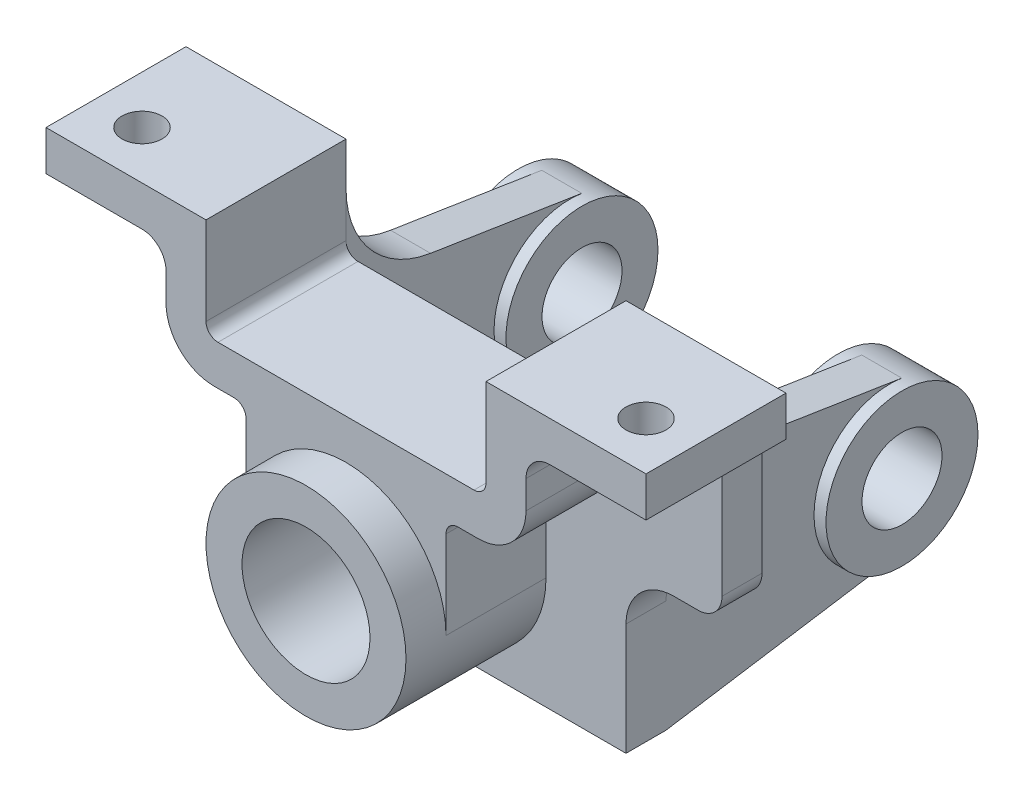
SolidWorks part; units mm, degrees
ref_plane "Ön Düzlem" through (0, 0, 0) normal (0, 0, 1) x (1, 0, 0)
ref_plane "Üst Düzlem" through (0, 0, 0) normal (0, 1, 0) x (1, 0, 0)
ref_plane "Sağ Düzlem" through (0, 0, 0) normal (1, 0, 0) x (0, 0, -1)
sketch "Çizim1" plane through (0, 0, 0) normal (0, 0, 1) x (1, 0, 0)
  circle A0 centre (0, 0) radius 16
  circle A1 centre (0, 0) radius 25
  dimension "D1" = 32
  dimension "D2" = 50
extrude "Yükseklik-Ekstrüzyon1" add sketch "Çizim1" against normal blind 45
ref_plane "Düzlem1" through (0, 0, -10) normal (0, 0, 1) x (1, 0, 0)
sketch "Çizim4" plane through (0, 0, -10) normal (0, 0, 1) x (1, 0, 0)
  line L0 (25, 0) -> (25, 22)
  line L1 (28, 25) -> (33, 25)
  line L2 (45, 37) -> (45, 44)
  line L3 (51, 50) -> (75, 50)
  line L4 (75, 50) -> (75, 60)
  line L5 (75, 60) -> (35, 60)
  line L6 (35, 60) -> (35, 38)
  line L7 (32, 35) -> (-32, 35)
  line L8 (0, 0) -> (0, 55.578) construction
  line L9 (-35, 60) -> (-35, 38)
  line L10 (-75, 60) -> (-35, 60)
  line L11 (-75, 50) -> (-75, 60)
  line L12 (-51, 50) -> (-75, 50)
  line L13 (-45, 37) -> (-45, 44)
  line L14 (-28, 25) -> (-33, 25)
  line L15 (-25, 0) -> (-25, 22)
  circle A0 centre (0, 0) radius 25 construction
  arc A1 (25, 22) -> (28, 25) centre (28, 22) cw
  arc A2 (33, 25) -> (45, 37) centre (33, 37) ccw
  arc A3 (45, 44) -> (51, 50) centre (51, 44) cw
  arc A4 (35, 38) -> (32, 35) centre (32, 38) cw
  arc A5 (-35, 38) -> (-32, 35) centre (-32, 38) ccw
  arc A6 (-45, 44) -> (-51, 50) centre (-51, 44) ccw
  arc A7 (-33, 25) -> (-45, 37) centre (-33, 37) cw
  arc A8 (-25, 22) -> (-28, 25) centre (-28, 22) ccw
  arc A9 (25, 0) -> (-25, 0) centre (0, 0) ccw
  point P23 (0, 35)
  dimension "D3" = 6
  dimension "D4" = 12
  dimension "D5" = 3
  dimension "D6" = 3
  dimension "D1" = 10
  dimension "D2" = 35
  dimension "D7" = 25
  dimension "D8" = 10
  dimension "D9" = 60
  dimension "D10" = 45
  dimension "D11" = 75
extrude "Yükseklik-Ekstrüzyon2" add sketch "Çizim4" against normal blind 35
sketch "Çizim5" plane through (0, 0, -45) normal (0, 0, -1) x (-1, 0, 0)
  line L0 (0, 0) -> (0, 88.279) construction
  line L1 (75, 50) -> (51, 50) construction
  line L2 (69, 50) -> (69, 18)
  line L3 (63, 12) -> (57, 12)
  line L4 (45, 0) -> (45, -28)
  line L5 (45, -28) -> (-45, -28)
  line L6 (25, 22) -> (25, 0) construction
  line L7 (33, 25) -> (28, 25) construction
  line L8 (45, 44) -> (45, 37) construction
  line L9 (25, 22) -> (25, 0)
  line L10 (33, 25) -> (28, 25)
  line L11 (45, 44) -> (45, 37)
  line L12 (69, 50) -> (51, 50)
  line L14 (-69, 50) -> (-51, 50)
  line L15 (-45, 44) -> (-45, 37)
  line L16 (-33, 25) -> (-28, 25)
  line L17 (-25, 22) -> (-25, 0)
  line L18 (-45, 0) -> (-45, -28)
  line L19 (-63, 12) -> (-57, 12)
  line L20 (-69, 50) -> (-69, 18)
  arc A0 (-25, 0) -> (25, 0) centre (0, 0) ccw construction
  arc A1 (28, 25) -> (25, 22) centre (28, 22) ccw construction
  arc A2 (33, 25) -> (45, 37) centre (33, 37) ccw construction
  arc A3 (51, 50) -> (45, 44) centre (51, 44) ccw construction
  arc A4 (-25, 0) -> (25, 0) centre (0, 0) ccw
  arc A5 (28, 25) -> (25, 22) centre (28, 22) ccw
  arc A6 (33, 25) -> (45, 37) centre (33, 37) ccw
  arc A7 (51, 50) -> (45, 44) centre (51, 44) ccw
  arc A8 (69, 18) -> (63, 12) centre (63, 18) cw
  arc A9 (57, 12) -> (45, 0) centre (57, 0) ccw
  arc A10 (-57, 12) -> (-45, 0) centre (-57, 0) cw
  arc A11 (-69, 18) -> (-63, 12) centre (-63, 18) ccw
  arc A12 (-51, 50) -> (-45, 44) centre (-51, 44) cw
  arc A13 (-33, 25) -> (-45, 37) centre (-33, 37) cw
  arc A14 (-28, 25) -> (-25, 22) centre (-28, 22) cw
  dimension "D1" = 6
  dimension "D2" = 12
  dimension "D3" = 69
  dimension "D4" = 38
  dimension "D5" = 40
  dimension "D6" = 45
extrude "Yükseklik-Ekstrüzyon4" add sketch "Çizim5" against normal blind 10 contours L5 L18 A10 L19 A11 L20 L14 A12 L15 A13 L16 A14 L17 A4 L9 A5 L10 A6 L11 A7 L12 L2 A8 L3 A9 L4
fillet "Radyus2" radius 6 2 edges at (-69, 50, -40) (69, 50, -40)
sketch "Çizim6" plane through (45, 0, 0) normal (1, 0, 0) x (0, 0, -1)
  line L0 (0, 0) -> (136.7815, 0) construction
  line L1 (35, 0) -> (35, -28) construction
  line L2 (45, -28) -> (103.9392, -18.7713)
  line L3 (45, 28) -> (103.9392, 18.7713)
  line L4 (45, 28) -> (45, -28)
  arc A0 (103.9392, -18.7713) -> (103.9392, 18.7713) centre (101, 0) ccw
  circle A1 centre (101, 0) radius 10
  dimension "D1" = 38
  dimension "D2" = 20
  dimension "D3" = 66
extrude "Yükseklik-Ekstrüzyon6" add sketch "Çizim6" against normal blind 10
ref_plane "Düzlem2" through (40, 0, 0) normal (1, 0, 0) x (0, 0, -1)
sketch "Çizim7" plane through (40, 0, 0) normal (1, 0, 0) x (0, 0, -1)
  circle A0 centre (101, 0) radius 10
  circle A1 centre (101, 0) radius 19
extrude "Yükseklik-Ekstrüzyon7" add sketch "Çizim7" along normal mid plane 16
fillet "Radyus3" radius 25 1 edges at (40, 28, -45)
mirror "Aynalama1" about plane through (0, 0, 0) normal (1, 0, 0) of "Yükseklik-Ekstrüzyon6", "Yükseklik-Ekstrüzyon7", "Radyus3"
sketch "Çizim8" plane through (0, 50, 0) normal (0, -1, 0) x (1, 0, 0)
  line L0 (63, -45) -> (57, -45) construction
  line L1 (75, -35) -> (75, -10) construction
  line L2 (0, -48.4) -> (0, 48.4) construction
  circle A0 centre (63, -22) radius 5
  circle A1 centre (-63, -22) radius 5
  dimension "D3" = 10
  dimension "D1" = 23
  dimension "D2" = 12
extrude "Kes-Ekstrüzyon1" cut sketch "Çizim8" against normal blind 16
